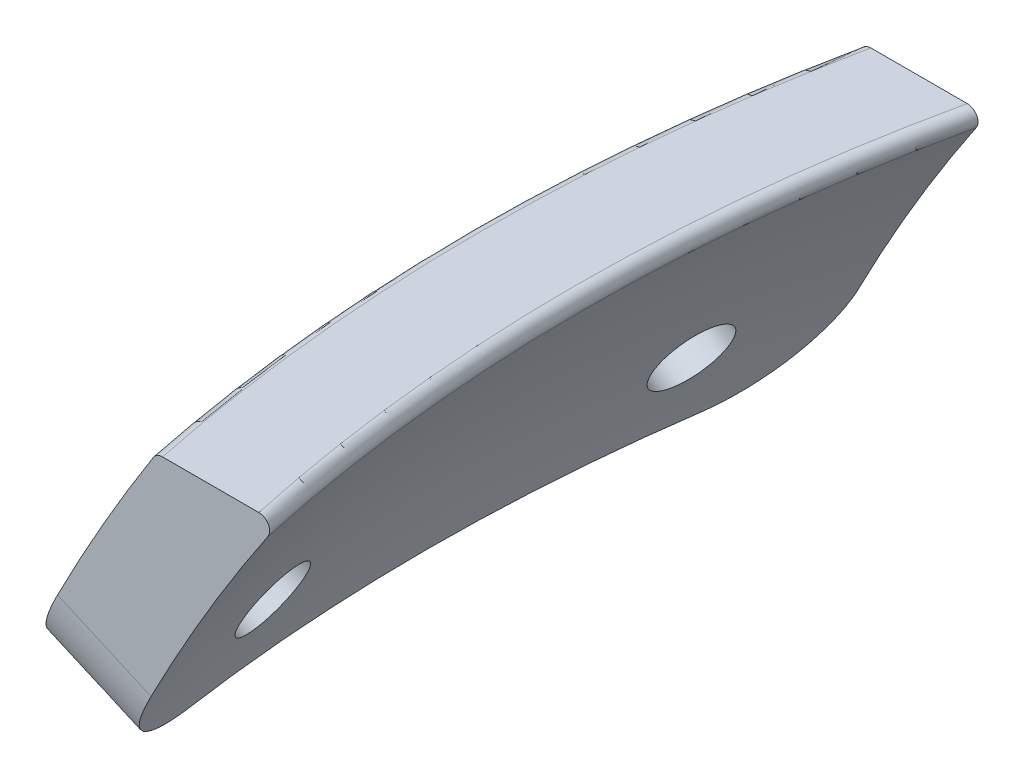
SolidWorks part; units mm, degrees
material "Polyether Polyol"
ref_plane "Front Plane" through (0, 0, 0) normal (0, 0, 1) x (1, 0, 0)
ref_plane "Top Plane" through (0, 0, 0) normal (0, 1, 0) x (1, 0, 0)
ref_plane "Right Plane" through (0, 0, 0) normal (1, 0, 0) x (0, 0, -1)
sketch "Sketch1" plane through (0, 0, 0) normal (0, 0, 1) x (1, 0, 0)
  line L2 (-166.6461, 194.6685) -> (-145.5262, 194.6685) construction
  line L3 (-179.8539, 169.9035) -> (-171.1512, 166.0318) construction
  line L6 (-166.6461, 194.6685) -> (-155.2793, 194.6685)
  line L7 (-179.8539, 169.9035) -> (-171.1512, 166.0318)
  line L8 (0, 0) -> (0, 244.1177) construction
  arc A1 (-161.2979, 185.1435) -> (-171.1512, 166.0318) centre (0, 89.8878) ccw construction
  arc A2 (-166.6461, 194.6685) -> (-179.8539, 169.9035) centre (0, 89.8878) ccw
  arc A3 (-162.991, 182.2165) -> (-171.1512, 166.0318) centre (0, 89.8878) ccw
  arc A4 (-162.991, 182.2165) -> (-155.2793, 194.6685) centre (0, 89.8878) cw
  point P1 (-162.991, 182.2165)
revolve "Revolve1" add sketch "Sketch1" angle 25 mid plane about L8
sketch "Sketch2" plane through (0, 0, 0) normal (0, 0, 1) x (1, 0, 0)
  line L0 (0, 89.8878) -> (-166.9078, 174.9315) construction
  line L1 (0, 0) -> (0, 244.1177) construction
  arc A1 (-162.991, 182.2165) -> (-171.1512, 166.0318) centre (0, 89.8878) ccw construction
  dimension "D1" = 63
ref_plane "Plane1" through (36.3604, 71.3612, 0) normal (0.454, 0.891, 0) x (-0.891, 0.454, 0)
sketch "Sketch4" plane through (36.3604, 71.3612, 0) normal (0.454, 0.891, 0) x (-0.891, 0.454, 0)
  line L0 (219.8801, 19.237) -> (239.1484, 20.9228) construction
  line L1 (219.5688, 22.7953) -> (238.8371, 24.4811)
  line L2 (219.5688, 22.7953) -> (219.8801, 19.237)
  line L3 (40.8082, 0) -> (228.1332, 0) construction
  line L4 (219.8801, 19.237) -> (239.1484, 20.9228)
  line L5 (238.8371, 24.4811) -> (239.1484, 20.9228)
  dimension "D1" = 7.1437
  dimension "D2" = 5
revolve "Cut-Revolve1" cut sketch "Sketch4" angle 360 about L0
mirror "Mirror1" about plane through (0, 0, 0) normal (0, 0, 1) of "Cut-Revolve1"
sketch "Sketch5" plane through (0, 0, 0) normal (0, 1, 0) x (1, 0, 0)
  line L1 (-151.5985, 33.6086) -> (-201.5408, 33.6086)
  line L2 (-151.5985, 33.6086) -> (-151.5985, -33.6086)
  line L3 (-151.5985, -33.6086) -> (-201.5408, -33.6086)
  line L4 (-201.5408, 33.6086) -> (-201.5408, -33.6086)
extrude "Cut-Extrude2" cut sketch "Sketch5" along normal through all flip side to cut
fillet "Fillet1" radius 10 2 edges
fillet "Fillet2" radius 1 2 edges at (-166.6461, 194.6685, 0) (-155.2793, 194.6685, 0)
